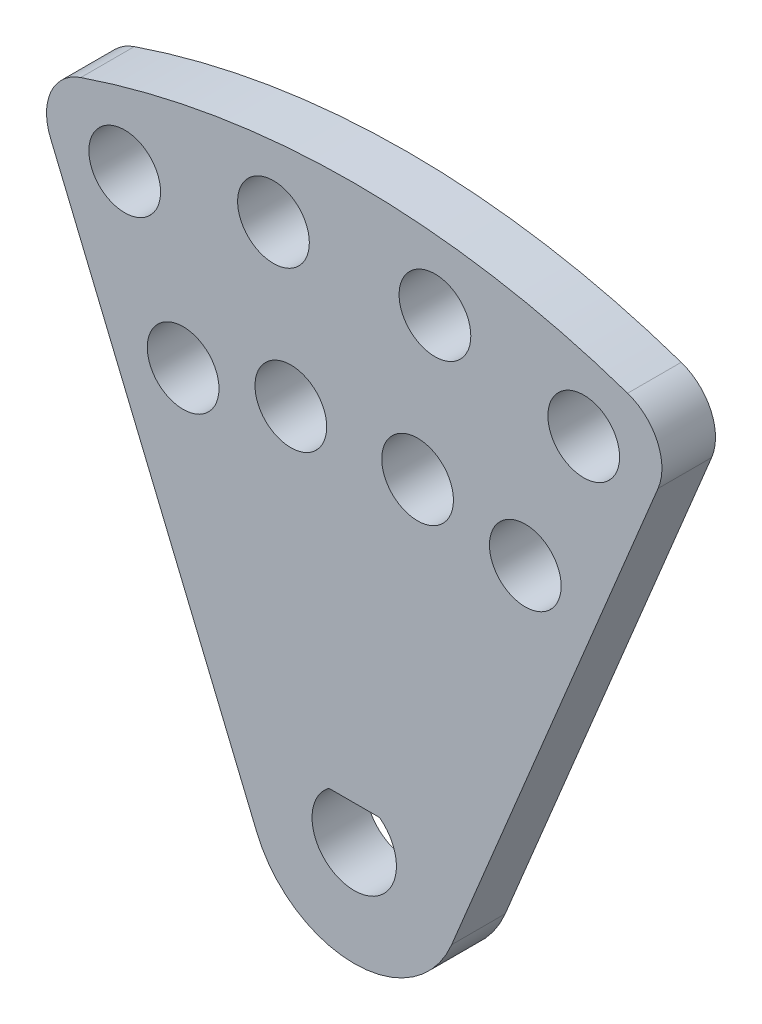
SolidWorks part; units mm, degrees
ref_plane "Front Plane" through (0, 0, 0) normal (0, 0, 1) x (1, 0, 0)
ref_plane "Top Plane" through (0, 0, 0) normal (0, 1, 0) x (1, 0, 0)
ref_plane "Right Plane" through (0, 0, 0) normal (1, 0, 0) x (0, 0, -1)
sketch "Sketch2" plane through (0, 0, 0) normal (0, 0, 1) x (1, 0, 0)
  line L0 (-3, 4) -> (3, 4)
  line L1 (-11.5485, -4.7835) -> (11.5485, -4.7835) construction
  line L2 (11.5485, -4.7835) -> (38.3827, 60)
  line L3 (-11.5485, -4.7835) -> (-38.3827, 60)
  line L4 (-38.3827, 60) -> (38.3827, 60) construction
  line L5 (0, -32.6641) -> (11.5485, -4.7835) construction
  line L6 (0, -32.6641) -> (-11.5485, -4.7835) construction
  arc A0 (-3, 4) -> (3, 4) centre (0, 0) ccw
  arc A1 (-11.5485, -4.7835) -> (11.5485, -4.7835) centre (0, 0) ccw
  arc A3 (-27.2033, 55.2221) -> (27.2033, 55.2221) centre (0, -32.6641) cw construction
  arc A4 (-38.3827, 60) -> (38.3827, 60) centre (0, -32.6641) cw
  circle A5 centre (-27.2033, 55.2221) radius 4.25
  circle A6 centre (-9.57, 58.8368) radius 4.25
  circle A7 centre (9.57, 58.8368) radius 4.25
  circle A8 centre (27.2033, 55.2221) radius 4.25
  arc A9 (-20.2782, 38.5033) -> (20.2782, 38.5033) centre (0, -32.6641) cw construction
  circle A10 centre (-20.2782, 38.5033) radius 4.25
  circle A11 centre (-7.5112, 40.9537) radius 4.25
  circle A12 centre (7.5112, 40.9537) radius 4.25
  circle A13 centre (20.2782, 38.5033) radius 4.25
  point P0 (0, 0)
  point P5 (0, 10)
  point P11 (0, -32.6641)
  point P14 (-9.57, 58.8368)
  point P15 (9.57, 58.8368)
  point P24 (-7.5112, 40.9537)
  point P25 (7.5112, 40.9537)
  dimension "D1" = 5
  dimension "D4" = 12.5
  dimension "D11" = 8.5
  dimension "D12" = 8.5
  dimension "D13" = 8.5
  dimension "D14" = 8.5
  dimension "D15" = 92
  dimension "D21" = 8.5
  dimension "D22" = 8.5
  dimension "D23" = 8.5
  dimension "D24" = 8.5
  dimension "D2" = 6
  dimension "D3" = 10
  dimension "D5" = 45
  dimension "D6" = 60
  dimension "D7" = 8.5
  dimension "D8" = 8.5
  dimension "D9" = 18
  dimension "D10" = 18
  dimension "D16" = 8.5
  dimension "D17" = 8.5
  dimension "D18" = 18
  dimension "D19" = 13
  dimension "D20" = 13
extrude "Boss-Extrude1" add sketch "Sketch2" along normal blind 6.35
fillet "Fillet1" radius 6 2 edges at (38.3827, 60, 3.175) (-38.3827, 60, 3.175)
equation "\"motorShaftDiameter\"= 10mm"
equation "\"motorShaftNotchLength\"= 6mm"
equation "\"D1@Sketch2\"=\"motorShaftDiameter\"/2"
equation "\"D2@Sketch2\"=\"motorShaftNotchLength\""
equation "\"tieRodHoleDiameter\"= 8.5mm"
equation "\"D7@Sketch2\"=\"tieRodHoleDiameter\""
equation "\"D8@Sketch2\"=\"tieRodHoleDiameter\""
equation "\"plateThickness\"= 25.4 / 4"
equation "\"D1@Boss-Extrude1\"=\"plateThickness\""
equation "\"D11@Sketch2\"=\"tieRodHoleDiameter\""
equation "\"D12@Sketch2\"=\"tieRodHoleDiameter\""
equation "\"D13@Sketch2\"=\"tieRodHoleDiameter\""
equation "\"D14@Sketch2\"=\"tieRodHoleDiameter\""
equation "\"D16@Sketch2\"=\"tieRodHoleDiameter\""
equation "\"D17@Sketch2\"=\"tieRodHoleDiameter\""
equation "\"D21@Sketch2\"=\"tieRodHoleDiameter\""
equation "\"D22@Sketch2\"=\"tieRodHoleDiameter\""
equation "\"D23@Sketch2\"=\"tieRodHoleDiameter\""
equation "\"D24@Sketch2\"=\"tieRodHoleDiameter\""
